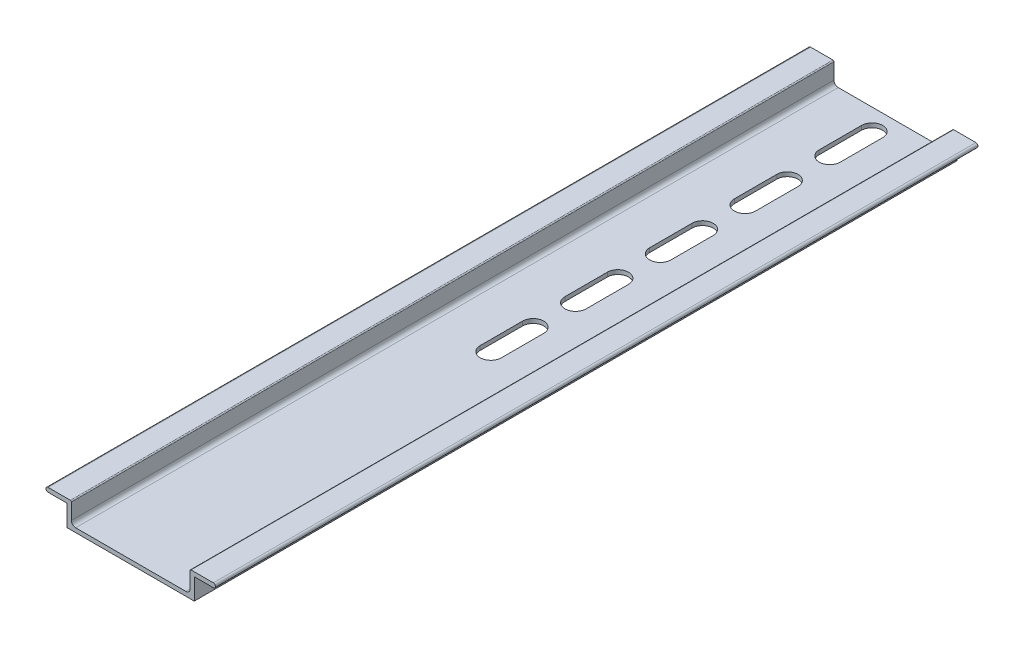
SolidWorks part; units mm, degrees
ref_plane "Front" through (0, 0, 0) normal (0, 0, 1) x (1, 0, 0)
ref_plane "Top" through (0, 0, 0) normal (0, 1, 0) x (1, 0, 0)
ref_plane "Right" through (0, 0, 0) normal (1, 0, 0) x (0, 0, -1)
sketch "Sketch1" plane through (0, 0, 0) normal (0, 0, 1) x (1, 0, 0)
  line L0 (-15, 0) -> (15, 0)
  line L1 (15, 0) -> (15, 5)
  line L2 (15, 5) -> (20, 5)
  line L3 (0, 0) -> (0, 7.8326) construction
  line L4 (-15, 5) -> (-20, 5)
  line L5 (-15, 0) -> (-15, 5)
  dimension "D1" = 30
  dimension "D2" = 5
  dimension "D3" = 5
extrude "Extrude-Thin1" add sketch "Sketch1" along normal mid plane 180 thin thin type one direction wall 1
fillet "Fillet1" radius 1 2 edges at (14, 1, 0) (-14, 1, 0)
fillet "Fillet2" radius 0.25 2 edges at (14, 6, 0) (-14, 6, 0)
fillet "Fillet3" 2 edges at (20, 6, 0) (20, 5, 0) type full round first side face at (17.125, 6, 0) second side face at (17.5, 5, 0) middle face at (20, 5.5, 0)
fillet "Fillet4" 2 edges at (-20, 6, 0) (-20, 5, 0) type full round first side face at (-17.125, 6, 0) second side face at (-17.5, 5, 0) middle face at (-20, 5.5, 0)
sketch "Sketch2" plane through (0, 1, 0) normal (0, 1, 0) x (1, 0, 0)
  line L0 (0, -5) -> (0, 5) construction
  line L1 (-2.5, -5) -> (-2.5, 5)
  line L2 (2.5, -5) -> (2.5, 5)
  arc A0 (-2.5, -5) -> (2.5, -5) centre (0, -5) ccw
  arc A1 (2.5, 5) -> (-2.5, 5) centre (0, 5) ccw
  point P2 (0, 0)
  dimension "D1" = 10
  dimension "D2" = 5
extrude "Cut-Extrude1" cut sketch "Sketch2" against normal through all
pattern_linear "LPattern1" count 5 spacing 20 along (0, 0, -1) of "Cut-Extrude1"
